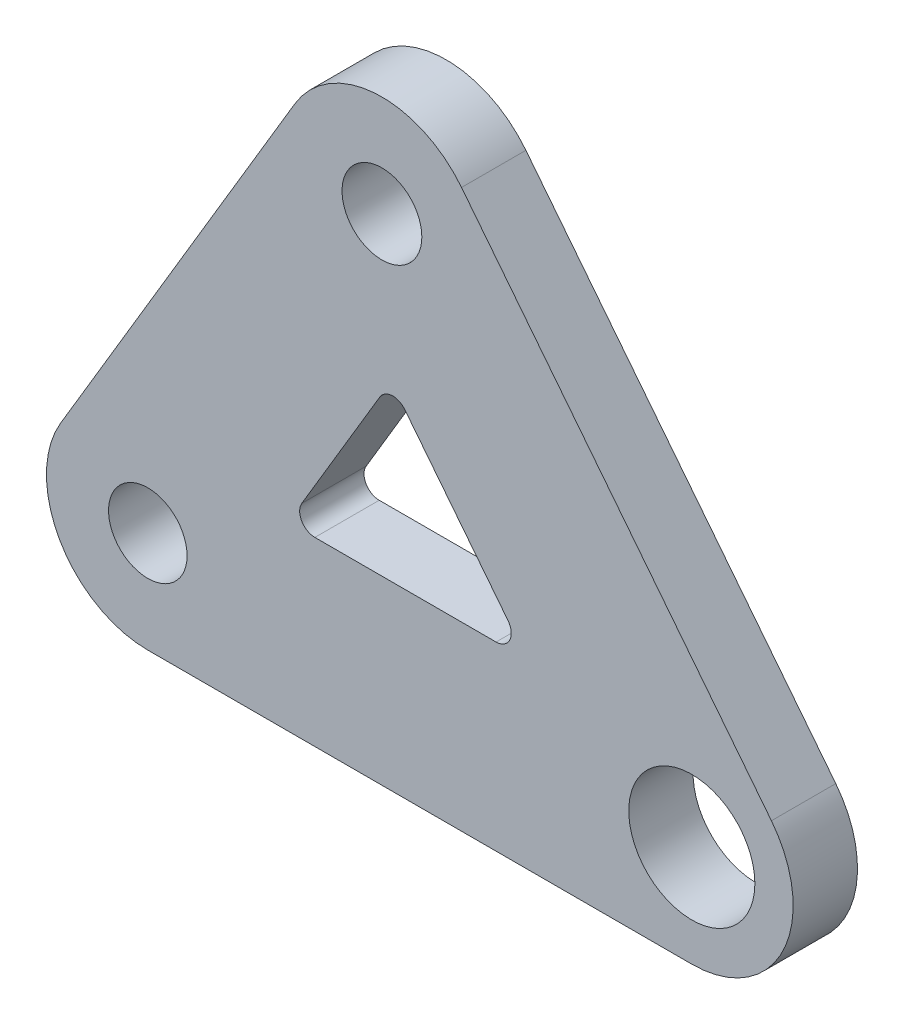
SolidWorks part; units mm, degrees
material "Balsa"
ref_plane "Front Plane" through (0, 0, 0) normal (0, 0, 1) x (1, 0, 0)
ref_plane "Top Plane" through (0, 0, 0) normal (0, 1, 0) x (1, 0, 0)
ref_plane "Right Plane" through (0, 0, 0) normal (1, 0, 0) x (0, 0, -1)
sketch "Sketch1" plane through (0, 0, 0) normal (0, 0, 1) x (1, 0, 0)
  line L0 (0, 0) -> (-23.1039, -38.8306) construction
  line L1 (-23.1039, -38.8306) -> (30.5799, -38.8306) construction
  line L2 (30.5799, -38.8306) -> (0, 0) construction
  line L6 (0.9059, -13.8786) -> (-9.2548, -30.9556)
  line L7 (-9.2548, -30.9556) -> (14.3543, -30.9556)
  line L8 (14.3543, -30.9556) -> (0.9059, -13.8786)
  line L9 (-31.6978, -33.7173) -> (-8.5939, 5.1133)
  line L10 (7.8563, 6.187) -> (38.4362, -32.6436)
  line L11 (-23.1039, -48.8306) -> (30.5799, -48.8306)
  circle A0 centre (0, 0) radius 3.9375
  circle A1 centre (-23.1039, -38.8306) radius 3.875
  circle A2 centre (30.5799, -38.8306) radius 6.223
  circle A6 centre (0, 0) radius 10
  circle A7 centre (30.5799, -38.8306) radius 10
  circle A8 centre (-23.1039, -38.8306) radius 10
  dimension "D2" = 7.75
  dimension "D3" = 12.446
  dimension "D6" = 53.6839
  dimension "D9" = 10
  dimension "D10" = 10
  dimension "D11" = 10
  dimension "D12" = 7.875
  dimension "D4" = 20
  dimension "D7" = 45.1841
  dimension "D8" = 49.4261
  dimension "D5" = 7.875
extrude "Boss-Extrude1" add sketch "Sketch1" along normal blind 6.35 contours A8 L11 A7 L10 A6 L9 L8 L7 L6 | A8 A1 | A6 A0 | A7 A2 region at (-19.3798, -14.7578, 0) region at (-20.5274, -29.4612, 0) region at (-0.6329, 9.6965, 0) region at (21.838, -34.5877, 0)
fillet "Fillet1" radius 1.5 3 edges at (14.3543, -30.9556, 3.175) (0.9059, -13.8786, 3.175) (-9.2548, -30.9556, 3.175)
